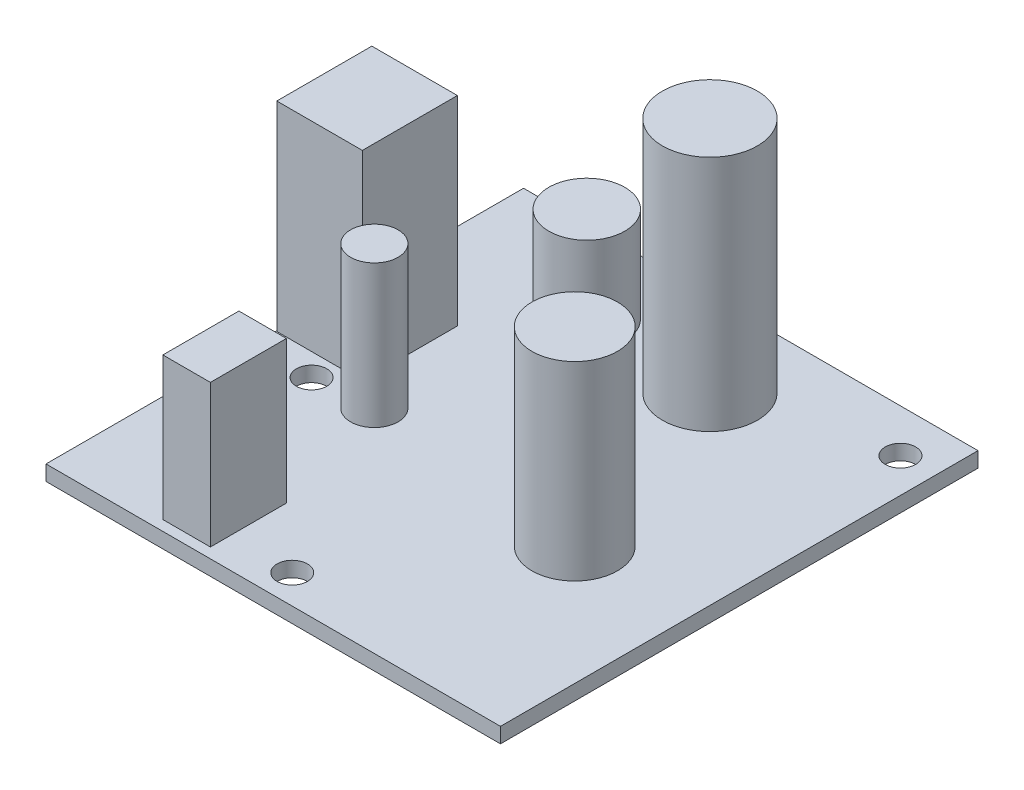
SolidWorks part; units mm, degrees
ref_plane "Front Plane" through (0, 0, 0) normal (0, 0, 1) x (1, 0, 0)
ref_plane "Top Plane" through (0, 0, 0) normal (0, 1, 0) x (1, 0, 0)
ref_plane "Right Plane" through (0, 0, 0) normal (1, 0, 0) x (0, 0, -1)
sketch "Sketch1" plane through (0, 0, 0) normal (0, 1, 0) x (1, 0, 0)
  line L1 (47.8143, 50.2404) -> (0, 50.2404)
  line L2 (47.8143, 50.2404) -> (47.8143, 0)
  line L3 (47.8143, 0) -> (0, 0)
  line L4 (0, 50.2404) -> (0, 0)
  line L5 (0.072, 34.21) -> (9.072, 34.21)
  line L6 (0.072, 34.21) -> (0.072, 24.21)
  line L7 (0.072, 24.21) -> (9.072, 24.21)
  line L8 (9.072, 34.21) -> (9.072, 24.21)
  line L9 (0.072, 34.21) -> (9.072, 24.21) construction
  line L10 (0.072, 24.21) -> (9.072, 34.21) construction
  line L11 (11.216, 1.08) -> (16.216, 1.08)
  line L12 (11.216, 1.08) -> (11.216, 9.08)
  line L13 (11.216, 9.08) -> (16.216, 9.08)
  line L14 (16.216, 1.08) -> (16.216, 9.08)
  line L15 (11.216, 1.08) -> (16.216, 9.08) construction
  line L16 (11.216, 9.08) -> (16.216, 1.08) construction
  circle A0 centre (28.448, 41.402) radius 5
  circle A1 centre (35.306, 20.32) radius 4.5
  circle A2 centre (12.192, 22.352) radius 2.5
  circle A3 centre (15.24, 41.656) radius 4
  circle A4 centre (6.096, 21.844) radius 1.6
  circle A5 centre (44.196, 45.7) radius 1.6
  circle A6 centre (22.86, 3.048) radius 1.6
  point P4 (28.448, 41.402)
  point P7 (4.572, 29.21)
  point P8 (4.572, 29.21)
  point P15 (35.306, 20.32)
  point P16 (13.716, 5.08)
  point P17 (13.716, 5.08)
  point P22 (12.192, 22.352)
  point P25 (15.24, 41.656)
  dimension "D5" = 10
  dimension "D12" = 9
  dimension "D19" = 5
  dimension "D22" = 8
  dimension "D23" = 3.2
  dimension "D26" = 45.7
  dimension "D1" = 50.2403
  dimension "D2" = 47.8143
  dimension "D3" = 19.3663
  dimension "D4" = 8.8384
  dimension "D6" = 43.2423
  dimension "D7" = 21.0303
  dimension "D8" = 9
  dimension "D9" = 10
  dimension "D10" = 35.306
  dimension "D11" = 20.32
  dimension "D13" = 13.716
  dimension "D14" = 5.08
  dimension "D15" = 8
  dimension "D16" = 5
  dimension "D17" = 12.192
  dimension "D18" = 22.352
  dimension "D20" = 15.24
  dimension "D21" = 41.656
  dimension "D24" = 6.096
  dimension "D25" = 21.844
  dimension "D27" = 44.196
  dimension "D28" = 3.048
  dimension "D29" = 22.86
extrude "Boss-Extrude3" add sketch "Sketch1" along normal blind 25 contours A0
extrude "Boss-Extrude4" add sketch "Sketch1<7>" along normal blind 21 separate body contours L8 L5 L6 L7 region at (4.572, 0, -29.21)
sketch "Sketch1<7>" plane through (0, 0, 0) normal (0, 1, 0) x (1, 0, 0) same geometry as "Sketch1"
extrude "Boss-Extrude5" add sketch "Sketch1<8>" along normal blind 20 contours A1 region at (35.306, 0, -20.32)
sketch "Sketch1<8>" plane through (0, 0, 0) normal (0, 1, 0) x (1, 0, 0) same geometry as "Sketch1"
extrude "Boss-Extrude6" add sketch "Sketch1<9>" along normal blind 15 separate body contours L11 L14 L13 L12 region at (13.716, 0, -5.08)
sketch "Sketch1<9>" plane through (0, 0, 0) normal (0, 1, 0) x (1, 0, 0) same geometry as "Sketch1"
extrude "Boss-Extrude7" add sketch "Sketch1<10>" along normal blind 15 separate body contours A2 region at (12.192, 0, -22.352)
sketch "Sketch1<10>" plane through (0, 0, 0) normal (0, 1, 0) x (1, 0, 0) same geometry as "Sketch1"
extrude "Boss-Extrude8" add sketch "Sketch1<11>" against normal blind 1.6 separate body
sketch "Sketch1<11>" plane through (0, 0, 0) normal (0, 1, 0) x (1, 0, 0) same geometry as "Sketch1"
extrude "Boss-Extrude9" add sketch "Sketch1<12>" along normal blind 10 separate body contours A3 region at (15.24, 0, -41.656)
sketch "Sketch1<12>" plane through (0, 0, 0) normal (0, 1, 0) x (1, 0, 0) same geometry as "Sketch1"
